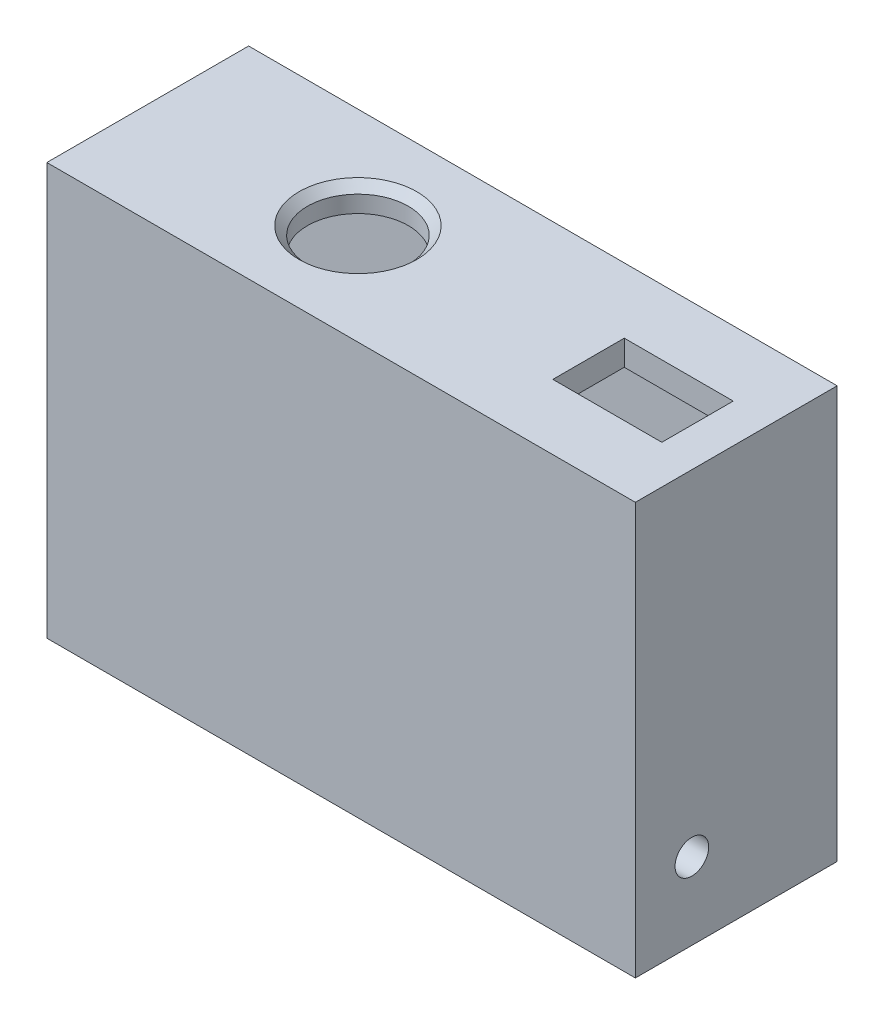
SolidWorks part; units mm, degrees
ref_plane "Front Plane" through (0, 0, 0) normal (0, 0, 1) x (1, 0, 0)
ref_plane "Top Plane" through (0, 0, 0) normal (0, 1, 0) x (1, 0, 0)
ref_plane "Right Plane" through (0, 0, 0) normal (1, 0, 0) x (0, 0, -1)
sketch "Sketch1" plane through (0, 0, 0) normal (0, 1, 0) x (1, 0, 0)
  line L0 (12.5, 6) -> (22.5, 6)
  line L1 (-12.5, 6) -> (12.5, 6)
  line L2 (-12.5, 6) -> (-12.5, -6)
  line L3 (-12.5, -6) -> (12.5, -6)
  line L5 (22.5, 6) -> (22.5, -6)
  line L6 (22.5, -6) -> (12.5, -6)
  line L8 (13.7159, 2.1231) -> (20.197, 2.1231)
  line L9 (13.7159, 2.1231) -> (13.7159, -2.1231)
  line L10 (13.7159, -2.1231) -> (20.197, -2.1231)
  line L11 (20.197, 2.1231) -> (20.197, -2.1231)
  circle A0 centre (0, 0) radius 3
  point P4 (0, 6)
  point P6 (-12.5, 0)
  point P15 (13.7159, 0)
  point P16 (22.5, 0)
  dimension "D3" = 6
  dimension "D1" = 25
  dimension "D2" = 12
  dimension "D4" = 10
extrude "Boss-Extrude1" add sketch "Sketch1" along normal blind 1.5
sketch "Sketch2" plane through (0, 0, 0) normal (0, 1, 0) x (1, 0, 0)
  line L1 (-12.5, 6) -> (22.5, 6)
  line L2 (-12.5, 6) -> (-12.5, -6)
  line L3 (-12.5, -6) -> (22.5, -6)
  line L4 (22.5, 6) -> (22.5, -6)
  line L5 (-11, 4.5) -> (21, 4.5)
  line L6 (-11, 4.5) -> (-11, -4.5)
  line L7 (-11, -4.5) -> (21, -4.5)
  line L8 (21, 4.5) -> (21, -4.5)
  point P10 (0, 0)
  point P11 (0, 0)
  point P13 (0, 0)
  dimension "D1" = 1.5
  dimension "D2" = 1.5
  dimension "D3" = 1.5
  dimension "D4" = 1.5
extrude "Boss-Extrude2" add sketch "Sketch2" against normal blind 23
chamfer "Chamfer1" distance 0.5 angle 45 1 edges at (0, 1.5, 3)
sketch "Sketch3" plane through (-12.5, 0, 0) normal (-1, 0, 0) x (0, 0, 1)
  circle A0 centre (2.6412, -18.4308) radius 1
  dimension "D1" = 2
extrude "Cut-Extrude1" cut sketch "Sketch3" against normal through all both and the other way through all
equation "\"wall\"=1.5"
equation "\"D1@Boss-Extrude1\"=\"wall\""
